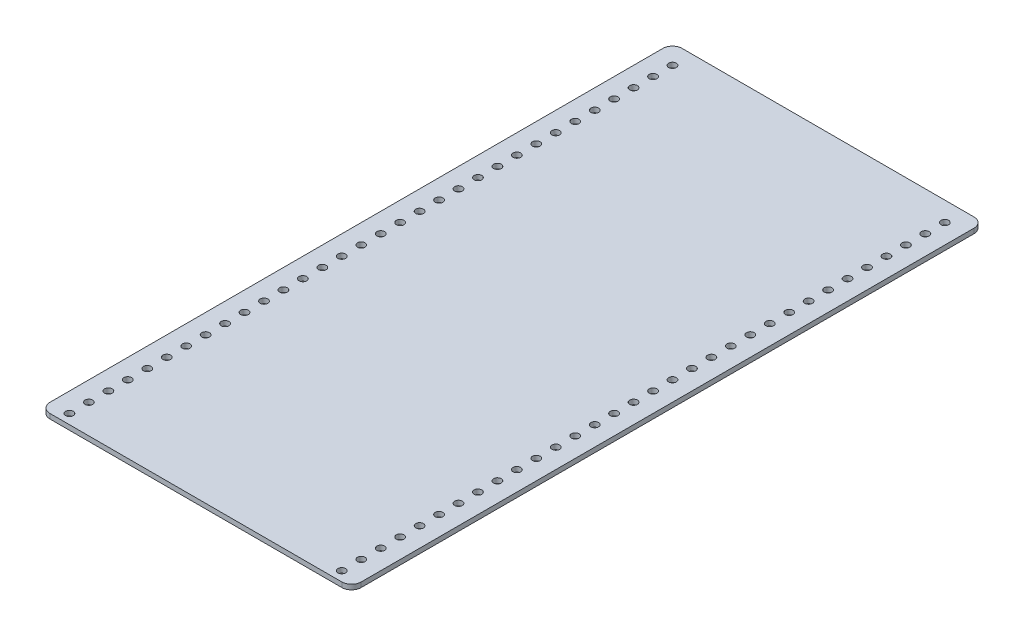
SolidWorks part; units mm, degrees
ref_plane "Front Plane" through (0, 0, 0) normal (0, 0, 1) x (1, 0, 0)
ref_plane "Top Plane" through (0, 0, 0) normal (0, 1, 0) x (1, 0, 0)
ref_plane "Right Plane" through (0, 0, 0) normal (1, 0, 0) x (0, 0, -1)
sketch "Sketch1" plane through (0, 0, 0) normal (0, 1, 0) x (1, 0, 0)
  line L1 (-77.8898, 294.359) -> (112.6102, 294.359)
  line L2 (-84.2398, 288.009) -> (-84.2398, -112.041)
  line L3 (-77.8898, -118.391) -> (112.6102, -118.391)
  line L4 (118.9602, 288.009) -> (118.9602, -112.041)
  arc A0 (-84.2398, -112.041) -> (-77.8898, -118.391) centre (-77.8898, -112.041) ccw
  arc A1 (112.6102, -118.391) -> (118.9602, -112.041) centre (112.6102, -112.041) ccw
  arc A2 (112.6102, 294.359) -> (118.9602, 288.009) centre (112.6102, 288.009) cw
  arc A3 (-77.8898, 294.359) -> (-84.2398, 288.009) centre (-77.8898, 288.009) ccw
  point P6 (-84.2398, -118.391)
  point P9 (118.9602, -118.391)
  point P14 (-84.2398, 294.359)
  dimension "D3" = 6.35
  dimension "D1" = 203.2
  dimension "D2" = 412.75
extrude "Boss-Extrude1" add sketch "Sketch1" along normal blind 3.175
sketch "Sketch3" plane through (0, 3.175, 0) normal (0, 1, 0) x (1, 0, 0)
  line L0 (118.9602, -112.041) -> (118.9602, 288.009) construction
  line L1 (112.6102, 294.359) -> (-77.8898, 294.359) construction
  line L2 (-84.2398, 288.009) -> (-84.2398, -112.041) construction
  circle A0 centre (-71.5398, 281.659) radius 2.5
  circle A1 centre (106.2602, 281.659) radius 2.5
  circle A2 centre (-71.5398, 268.959) radius 2.5
  circle A3 centre (106.2602, 268.959) radius 2.5
  circle A4 centre (-71.5398, 256.259) radius 2.5
  circle A5 centre (106.2602, 256.259) radius 2.5
  circle A6 centre (-71.5398, 243.559) radius 2.5
  circle A7 centre (106.2602, 243.559) radius 2.5
  circle A8 centre (-71.5398, 230.859) radius 2.5
  circle A9 centre (106.2602, 230.859) radius 2.5
  circle A10 centre (-71.5398, 218.159) radius 2.5
  circle A11 centre (106.2602, 218.159) radius 2.5
  circle A12 centre (-71.5398, 205.459) radius 2.5
  circle A13 centre (106.2602, 205.459) radius 2.5
  circle A14 centre (-71.5398, 192.759) radius 2.5
  circle A15 centre (106.2602, 192.759) radius 2.5
  circle A16 centre (-71.5398, 180.059) radius 2.5
  circle A17 centre (106.2602, 180.059) radius 2.5
  circle A18 centre (-71.5398, 167.359) radius 2.5
  circle A19 centre (106.2602, 167.359) radius 2.5
  circle A20 centre (-71.5398, 154.659) radius 2.5
  circle A21 centre (106.2602, 154.659) radius 2.5
  circle A22 centre (-71.5398, 141.959) radius 2.5
  circle A23 centre (106.2602, 141.959) radius 2.5
  circle A24 centre (-71.5398, 129.259) radius 2.5
  circle A25 centre (106.2602, 129.259) radius 2.5
  circle A26 centre (-71.5398, 116.559) radius 2.5
  circle A27 centre (106.2602, 116.559) radius 2.5
  circle A28 centre (-71.5398, 103.859) radius 2.5
  circle A29 centre (106.2602, 103.859) radius 2.5
  circle A30 centre (-71.5398, 91.159) radius 2.5
  circle A31 centre (106.2602, 91.159) radius 2.5
  circle A32 centre (-71.5398, 78.459) radius 2.5
  circle A33 centre (106.2602, 78.459) radius 2.5
  circle A34 centre (-71.5398, 65.759) radius 2.5
  circle A35 centre (106.2602, 65.759) radius 2.5
  circle A36 centre (-71.5398, 53.059) radius 2.5
  circle A37 centre (106.2602, 53.059) radius 2.5
  circle A38 centre (-71.5398, 40.359) radius 2.5
  circle A39 centre (106.2602, 40.359) radius 2.5
  circle A40 centre (-71.5398, 27.659) radius 2.5
  circle A41 centre (106.2602, 27.659) radius 2.5
  circle A42 centre (-71.5398, 14.959) radius 2.5
  circle A43 centre (106.2602, 14.959) radius 2.5
  circle A44 centre (-71.5398, 2.259) radius 2.5
  circle A45 centre (106.2602, 2.259) radius 2.5
  circle A46 centre (-71.5398, -10.441) radius 2.5
  circle A47 centre (106.2602, -10.441) radius 2.5
  circle A48 centre (-71.5398, -23.141) radius 2.5
  circle A49 centre (106.2602, -23.141) radius 2.5
  circle A50 centre (-71.5398, -35.841) radius 2.5
  circle A51 centre (106.2602, -35.841) radius 2.5
  circle A52 centre (-71.5398, -48.541) radius 2.5
  circle A53 centre (106.2602, -48.541) radius 2.5
  circle A54 centre (-71.5398, -61.241) radius 2.5
  circle A55 centre (106.2602, -61.241) radius 2.5
  circle A56 centre (-71.5398, -73.941) radius 2.5
  circle A57 centre (106.2602, -73.941) radius 2.5
  circle A58 centre (-71.5398, -86.641) radius 2.5
  circle A59 centre (106.2602, -86.641) radius 2.5
  circle A60 centre (-71.5398, -99.341) radius 2.5
  circle A61 centre (106.2602, -99.341) radius 2.5
  circle A62 centre (-71.5398, -112.041) radius 2.5
  circle A63 centre (106.2602, -112.041) radius 2.5
  circle A64 centre (-71.5398, -124.741) radius 2.5
  circle A65 centre (106.2602, -124.741) radius 2.5
  circle A66 centre (-71.5398, -137.441) radius 2.5
  circle A67 centre (106.2602, -137.441) radius 2.5
  circle A68 centre (-71.5398, -150.141) radius 2.5
  circle A69 centre (106.2602, -150.141) radius 2.5
  dimension "D1" = 5
  dimension "D2" = 5
  dimension "D3" = 12.7
  dimension "D4" = 12.7
  dimension "D5" = 12.7
  dimension "D6" = 12.7
  dimension "D7" = 35
extrude "Cut-Extrude2" cut sketch "Sketch3" against normal through all
